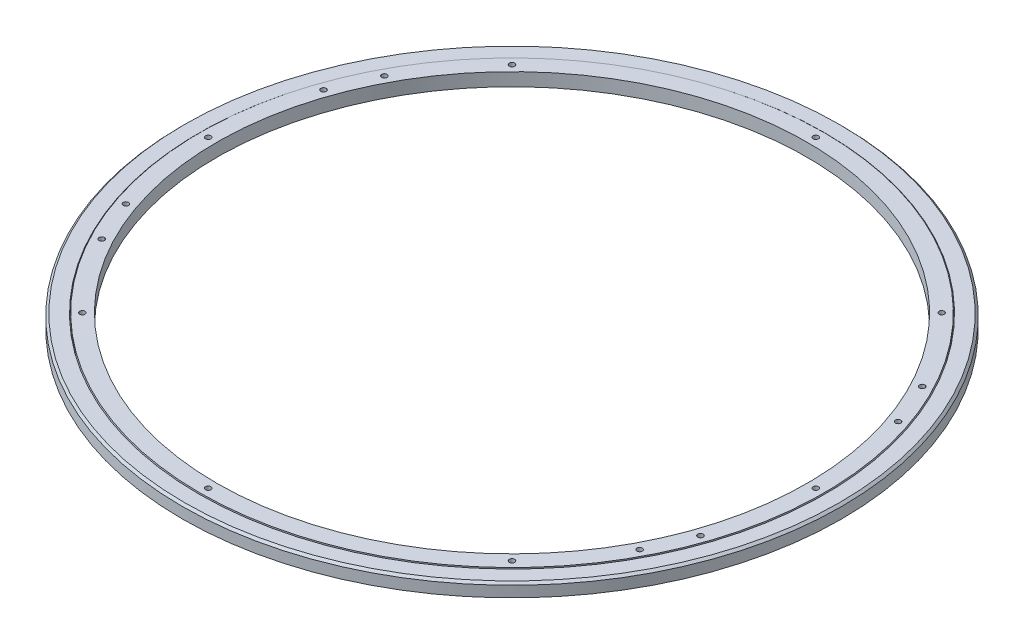
SolidWorks part; units mm, degrees
note: '?' marks a value the reader was unsure of.
ref_plane "Front" through (0, 0, 0) normal (0, 0, 1) x (1, 0, 0)
ref_plane "Top" through (0, 0, 0) normal (0, 1, 0) x (1, 0, 0)
ref_plane "Right" through (0, 0, 0) normal (1, 0, 0) x (0, 0, -1)
ref_axis "Axis1" through (0, 273.2172, 0) along (0, -1, 0)?
sketch "Sketch1" plane through (0, 0, 0) normal (0, 0, 1) x (1, 0, 0)
  line L0 (0, 11.4758) -> (0, -9.8104) construction
  line L1 (-350, 0.7938) -> (-350, 259.4887) construction
  line L2 (-379.9875, 0) -> (-340.3375, -14.2875) construction
  line L3 (-359.6625, 0.7938) -> (-359.6625, -3.9324)
  line L4 (-359.6625, -14.2875) -> (-340.3375, -14.2875)
  line L5 (-340.3375, 0.7937) -> (-340.3375, -14.2875)
  line L6 (-360.6625, 0) -> (-379.9875, 0)
  line L7 (-360.6625, 0) -> (-360.6625, -3.9324)
  line L8 (350, 259.4888) -> (-350, 259.4888) construction
  line L9 (-379.9875, 0) -> (-379.9875, -15.0812)
  line L15 (-359.6625, 0.7938) -> (-340.3375, 0.7937)
  line L16 (-360.6625, -15.0812) -> (-379.9875, -15.0812)
  line L18 (-360.6625, -10.3551) -> (-360.6625, -15.0812)
  line L19 (-359.6625, -10.3551) -> (-359.6625, -14.2875)
  arc A0 (-360.6625, -3.9324) -> (-360.6625, -10.3551) centre (-360.1625, -7.1437) ccw
  arc A1 (-359.6625, -10.3551) -> (-359.6625, -3.9324) centre (-360.1625, -7.1437) ccw
  dimension "D8" = 6.5
  dimension "D1" = 39.65
  dimension "D2" = 15.0812
  dimension "D3" = 15.875
  dimension "D4" = 759.975
  dimension "D5" = 1
revolve "Revolve1" add sketch "Sketch1" angle 360 about L0
sketch "Sketch11" plane through (0, 0, 0) normal (0, 1, 0) x (1, 0, 0)
  circle A4 centre (0, 0) radius 389.5125
  circle A5 centre (0, 0) radius 389.5125 construction
  dimension "D1" = 9.525
sketch "Sketch3" plane through (0, 0.7937, 0) normal (0, 1, 0) x (-1, 0, 0)
  line L0 (38.1046, 0) -> (-45.2941, 0) construction
  circle A0 centre (0, -389.5125) radius 3.1
  circle A2 centre (0, 0) radius 389.5125 construction
  dimension "D1" = 6.2
extrude "Cut-Extrude1" cut sketch "Sketch3" against normal blind 12.8
pattern_circular "CirPattern1" count 10 over 360 about axis through (0, 273.2172, 0) along (0, -1, 0)
sketch "Sketch12" plane through (0, 0.7937, 0) normal (0, 1, 0) x (1, 0, 0)
  circle A1 centre (0, 0) radius 350.1375
  circle A2 centre (0, 0) radius 350.1375
  dimension "D1" = 9.525
sketch "Sketch4" plane through (0, -15.0812, 0) normal (0, -1, 0) x (1, 0, 0)
  line L0 (-19.4118, 0) -> (22.2876, 0) construction
  circle A0 centre (0, -350.1375) radius 3.1
  circle A1 centre (0, 0) radius 350.1375 construction
  dimension "D1" = 6.2
extrude "Cut-Extrude2" cut sketch "Sketch4" against normal up to next
pattern_circular "CirPattern2" count 8 over 360 about axis through (0, 0, 0) along (0, 1, 0) of "Cut-Extrude2"
sketch "Sketch9" plane through (0, 0, 0) normal (0, 1, 0) x (-1, 0, 0)
  line L0 (0, 0) -> (-243.5536, 0) construction
  line L1 (0, 0) -> (-323.4849, 133.9918) construction
  circle A0 centre (0, 0) radius 350.1375 construction
  circle A1 centre (-323.4849, 133.9918) radius 2.35
  point P2 (-247.5846, -247.5846)
  point P3 (0, 350.1375)
  point P5 (-247.5846, 247.5846)
  point P9 (-350.1375, 0)
  dimension "D1" = 4.7
  dimension "D2" = 22.5
extrude "Cut-Extrude5" cut sketch "Sketch9" against normal through all
chamfer "Chamfer2" distance 2.54 angle 45 1 edges at (0, 0, 379.9875)
pattern_circular "CirPattern7" count 4 over 360 about axis through (0, 0, 0) along (0, 1, 0) of "Cut-Extrude5"
ref_axis "Axis2" through (0, 0.7937, -350.1375) along (0, -1, 0)?
sketch "Sketch7" plane through (0, 0, 0) normal (1, 0, 0) x (0, 0, -1)
  line L0 (350.1375, -3.1155) -> (350.1375, -2.9) construction
  line L1 (350.1375, -3.1155) -> (353.1381, -3.1155)
  line L2 (353.1381, -3.1155) -> (353.1381, 0.8953)
  line L3 (353.1381, 0.8953) -> (355.2429, 0.8953)
  line L4 (355.2429, 0.8953) -> (355.2429, 3.3845)
  line L5 (355.2429, 3.3845) -> (350.1375, 3.3845)
  line L6 (350.1375, 3.3845) -> (350.1375, -3.1155)
  line L8 (353.2375, 0.7937) -> (347.0375, 0.7937) construction
  line L10 (350.1375, 0.7937) -> (350.1375, -14.2875) construction
  dimension "D1" = 6.5
  dimension "D2" = 0.1016
  dimension "D3" = 5.1054
  dimension "D4" = 2.4892
  dimension "D5" = 3.0006
revolve "Revolve3" [suppressed] add sketch "Sketch7" angle 360 about L0
pattern_circular "CirPattern5" [suppressed] count 8 over 360 about axis through (0, 273.2172, 0) along (0, -1, 0)
hole_wizard "3/8 Clearance Hole1" [suppressed] positions "Sketch14" profile "Sketch15" hole size "3/8" standard "ANSI Inch"
sketch "Sketch14" [suppressed] plane through (0, 0, 0) normal (0, 1, 0) x (1, 0, 0)
  circle A1 centre (0, 0) radius 333.375 construction
  circle A2 centre (-235.7317, 235.7317) radius 5.1054 construction
  point P0 (-235.7317, 235.7317)
sketch "Sketch15" plane through (-235.7317, 0, -235.7317) normal (1, 0, 0) x (0, 0, -1)
  line L0 (0, 0) -> (0, 3.3845)
  line L1 (0, 3.3845) -> (5.1587, 3.3845)
  line L2 (5.1587, 3.3845) -> (5.1587, 0)
  line L5 (5.1587, 0) -> (0, 0)
  line L11 (0, -6.35) -> (0, 107.95) construction
  dimension "Thru Hole Dia." = 10.3175
  dimension "Thru Hole Depth" = 3.3845
sketch "Sketch17" plane through (0, 0, 0) normal (0, 1, 0) x (1, 0, 0)
  circle A0 centre (-309.9518, 162.8684) radius 3.1
  circle A1 centre (-331.0992, 113.8841) radius 3.1
  circle A2 centre (0, 350.1375) radius 3.1 construction
  circle A3 centre (0, 0) radius 350.1375 construction
extrude "Cut-Extrude6" cut sketch "Sketch17" against normal through all and the other way through all contours A0 | A1
mirror "Mirror1" about plane through (0, 0, 0) normal (1, 0, 0) of "Cut-Extrude6"
mirror "Mirror2" about plane through (0, 0, 0) normal (0, 0, 1) of "Mirror1", "Cut-Extrude6"
